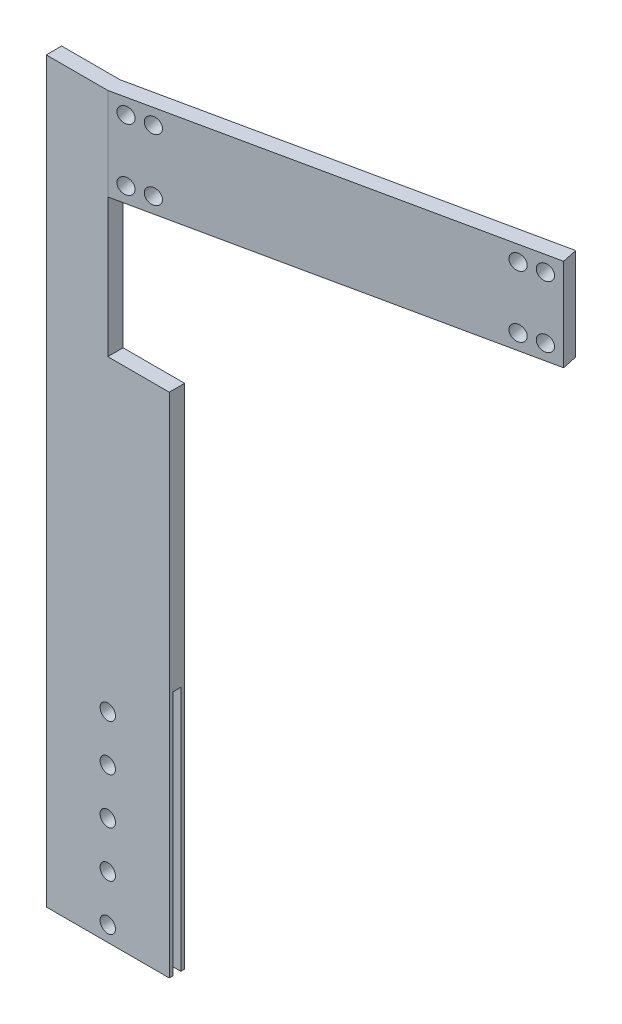
SolidWorks part; units mm, degrees
ref_plane "Front Plane" through (0, 0, 0) normal (0, 0, 1) x (1, 0, 0)
ref_plane "Top Plane" through (0, 0, 0) normal (0, 1, 0) x (1, 0, 0)
ref_plane "Right Plane" through (0, 0, 0) normal (1, 0, 0) x (0, 0, -1)
sketch "Sketch1" plane through (0, 0, 0) normal (0, 1, 0) x (1, 0, 0)
  line L0 (0, 23.6458) -> (0, -25.0113) construction
  line L1 (40, 5) -> (-40, 5)
  line L2 (-40, 5) -> (-40, 2.5)
  line L3 (-40, 2.5) -> (-30, 2.5)
  line L4 (-30, 2.5) -> (-30, -2.5)
  line L5 (-30, -2.5) -> (-40, -2.5)
  line L6 (-40, -2.5) -> (-40, -5)
  line L7 (-40, -5) -> (40, -5)
  line L8 (-30, 0) -> (30, 0) construction
  line L9 (40, -2.5) -> (40, -5)
  line L10 (30, -2.5) -> (40, -2.5)
  line L11 (30, 2.5) -> (30, -2.5)
  line L12 (40, 2.5) -> (30, 2.5)
  line L13 (40, 5) -> (40, 2.5)
  point P18 (0, -5)
  point P23 (0, 5)
  dimension "D1" = 2.5
  dimension "D2" = 10
  dimension "D3" = 10
  dimension "D4" = 80
extrude "body" add sketch "Sketch1" along normal blind 160
sketch "Sketch2" plane through (0, 0, 5) normal (0, 0, 1) x (1, 0, 0)
  line L0 (0, 0) -> (0, 160) construction
  line L1 (-40, 160) -> (40, 160) construction
  circle A0 centre (0, 10) radius 5
  dimension "D1" = 10
  dimension "D2" = 10
extrude "pin hole" cut sketch "Sketch2" against normal through all
pattern_linear "LPattern1" count 5 spacing 30 along (0, 1, 0) of "pin hole"
sketch "Sketch3" plane through (0, 0, 5) normal (0, 0, 1) x (1, 0, 0)
  line L1 (-40, 160) -> (40, 160)
  line L2 (-40, 160) -> (-40, 330)
  line L3 (-40, 330) -> (40, 330)
  line L4 (40, 160) -> (40, 330)
  line L5 (0, 330) -> (-40, 330)
  line L6 (0, 330) -> (0, 480)
  line L7 (0, 480) -> (-40, 480)
  line L8 (-40, 330) -> (-40, 480)
  point P4 (0, 0)
  point P12 (0, 330)
  line M13 (40, 160) -> (-40, 160)
  dimension "D1" = 170
  dimension "D2" = 150
  dimension "D3" = 40
extrude "spine" add sketch "Sketch3" against normal up to surface (10 mm away) contours L4 L3 L2 M13 | L3 L8 L7 L6 region at (0, 245, 5) region at (-20, 405, 5) up to face at (5, 40, -5)
sketch "Sketch8" plane through (0, 480, 0) normal (0, 1, 0) x (1, 0, 0)
  line L0 (0, -5) -> (244.5369, 46.9779)
  line L1 (244.5369, 46.9779) -> (242.4113, 56.9779)
  line L2 (242.4113, 56.9779) -> (-2.1256, 5)
  line L3 (-40, 5) -> (0, 5) construction
  line L4 (-2.1256, 5) -> (0, -5)
  line L5 (0, -5) -> (40, -5) construction
  line L6 (0, -5) -> (-40, -5) construction
  point P9 (5.9624, -5)
  point P12 (0, 0)
  dimension "D1" = 12
  dimension "D2" = 250
extrude "slider holder" add sketch "Sketch8" against normal blind 60
sketch "Sketch9" plane through (1.0168, 0, 4.7839) normal (0.2079, 0, 0.9781) x (0.9781, 0, -0.2079)
  line L0 (-1.0396, 450) -> (248.9604, 450) construction
  line L1 (-1.0396, 420) -> (-1.0396, 480) construction
  line L2 (248.9604, 420) -> (248.9604, 480) construction
  line L3 (123.9604, 420) -> (123.9604, 480) construction
  line L4 (-1.0396, 420) -> (248.9604, 420) construction
  line L5 (-1.0396, 480) -> (248.9604, 480) construction
  circle A0 centre (8.9604, 470) radius 5
  circle A1 centre (23.9604, 470) radius 5
  circle A2 centre (8.9604, 430) radius 5
  circle A3 centre (23.9604, 430) radius 5
  circle A4 centre (223.9604, 430) radius 5
  circle A5 centre (238.9604, 430) radius 5
  circle A6 centre (238.9604, 470) radius 5
  circle A7 centre (223.9604, 470) radius 5
  point P20 (29.2414, 439.9994)
  dimension "D1" = 10
  dimension "D2" = 20
  dimension "D3" = 15
  dimension "D4" = 10
extrude "slider fixture holes" cut sketch "Sketch9" against normal through all
